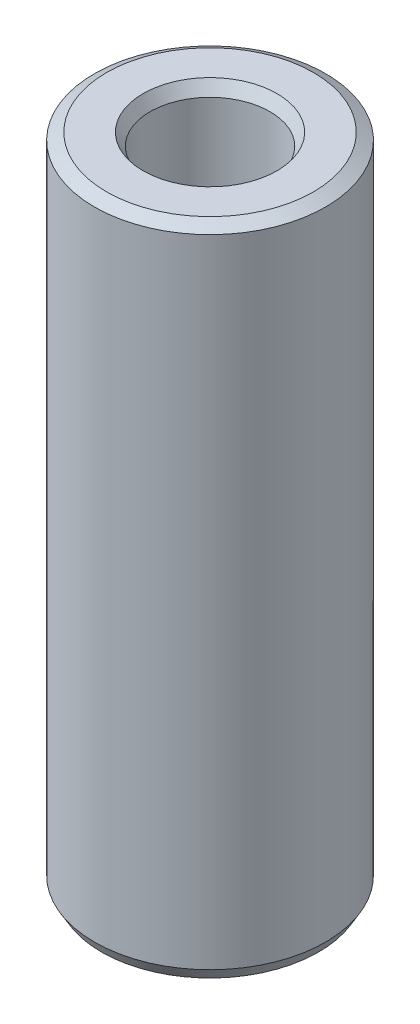
SolidWorks part; units mm, degrees
ref_plane "Front Plane" through (0, 0, 0) normal (0, 0, 1) x (1, 0, 0)
ref_plane "Top Plane" through (0, 0, 0) normal (0, 1, 0) x (1, 0, 0)
ref_plane "Right Plane" through (0, 0, 0) normal (1, 0, 0) x (0, 0, -1)
sketch "Sketch1" plane through (0, 0, 0) normal (0, 1, 0) x (1, 0, 0)
  circle A0 centre (0, 0) radius 20
  dimension "SLEEVE_OD" = 40
extrude "Boss-Extrude1" add sketch "Sketch1" along normal blind 113.4872
sketch "Sketch2" plane through (0, 0, 0) normal (0, 1, 0) x (1, 0, 0)
  circle A0 centre (0, 0) radius 10.37
  dimension "BORE_D" = 20.74
extrude "Cut-Extrude1" cut sketch "Sketch2" along normal through all
chamfer "Chamfer1" distance 1.2138 angle 60 4 edges at (0, 113.4872, 10.37) (0, 0, 10.37) (0, 0, 20) (0, 113.4872, 20) first distance on face at (0, 113.4872, 10.37) first distance on face at (0, 0, 10.37) first distance on face at (0, 113.4872, 20)
